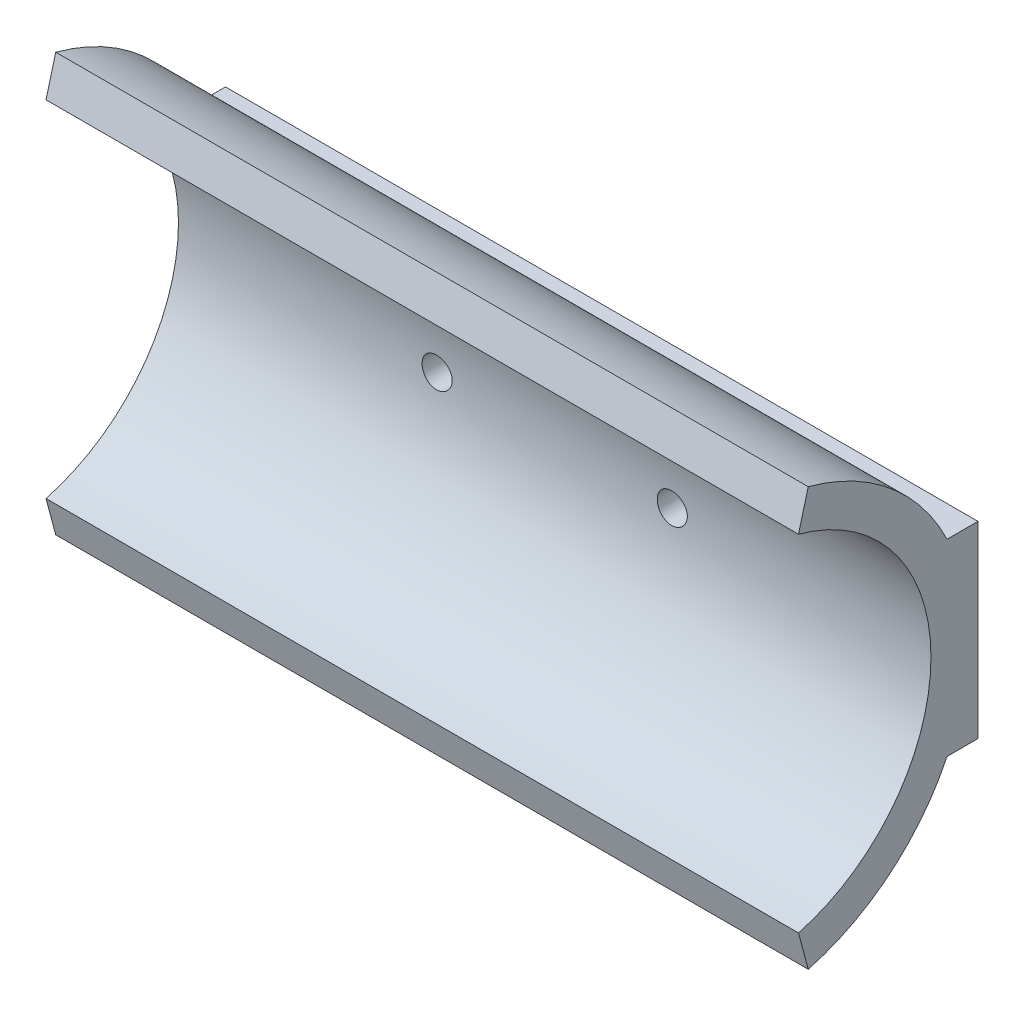
SolidWorks part; units mm, degrees
ref_plane "Front Plane" through (0, 0, 0) normal (1, 0, 0) x (0, 1, 0)
ref_plane "Top Plane" through (0, 0, 0) normal (0, 0, 1) x (0, 1, 0)
ref_plane "Right Plane" through (0, 0, 0) normal (0, 1, 0) x (-1, 0, 0)
sketch "Sketch1" plane through (0, 0, 0) normal (1, 0, 0) x (0, 1, 0)
  line L0 (18.3526, -4.9176) -> (22.2163, -5.9528)
  line L1 (-18.3526, -4.9176) -> (-22.2163, -5.9528)
  line L2 (0, 0) -> (57.6225, -15.4399) construction
  line L3 (0, 0) -> (38.6244, 0) construction
  line L4 (0, 0) -> (-49.8321, -13.3525) construction
  line L7 (-10, -20.7123) -> (-10, -24)
  line L8 (-10, -24) -> (10, -24)
  line L9 (10, -20.7123) -> (10, -24)
  line L10 (-10, -19) -> (10, -24) construction
  line L11 (-10, -24) -> (10, -19) construction
  arc A0 (-18.3526, -4.9176) -> (18.3526, -4.9176) centre (0, 0) ccw
  arc A1 (-22.2163, -5.9528) -> (-10, -20.7123) centre (0, 0) ccw
  arc A2 (10, -20.7123) -> (22.2163, -5.9528) centre (0, 0) ccw
  point P12 (0, -21.5)
  point P17 (0, 0)
  dimension "D1" = 19
  dimension "D2" = 23
  dimension "D3" = 5
  dimension "D4" = 15
  dimension "D5" = 15
  dimension "D6" = 20
  dimension "D7" = 24
extrude "Boss-Extrude1" add sketch "Sketch1" along normal mid plane 80
sketch "Sketch2" plane through (0, 0, -24) normal (0, 0, -1) x (-1, 0, 0)
  line L0 (0, 0) -> (0, 14.4324) construction
  circle A0 centre (12.5, 0) radius 1.6
  circle A1 centre (-12.5, 0) radius 1.6
  dimension "D2" = 3.2
  dimension "D1" = 12.5
extrude "Cut-Extrude1" cut sketch "Sketch2" against normal through all both and the other way through all
